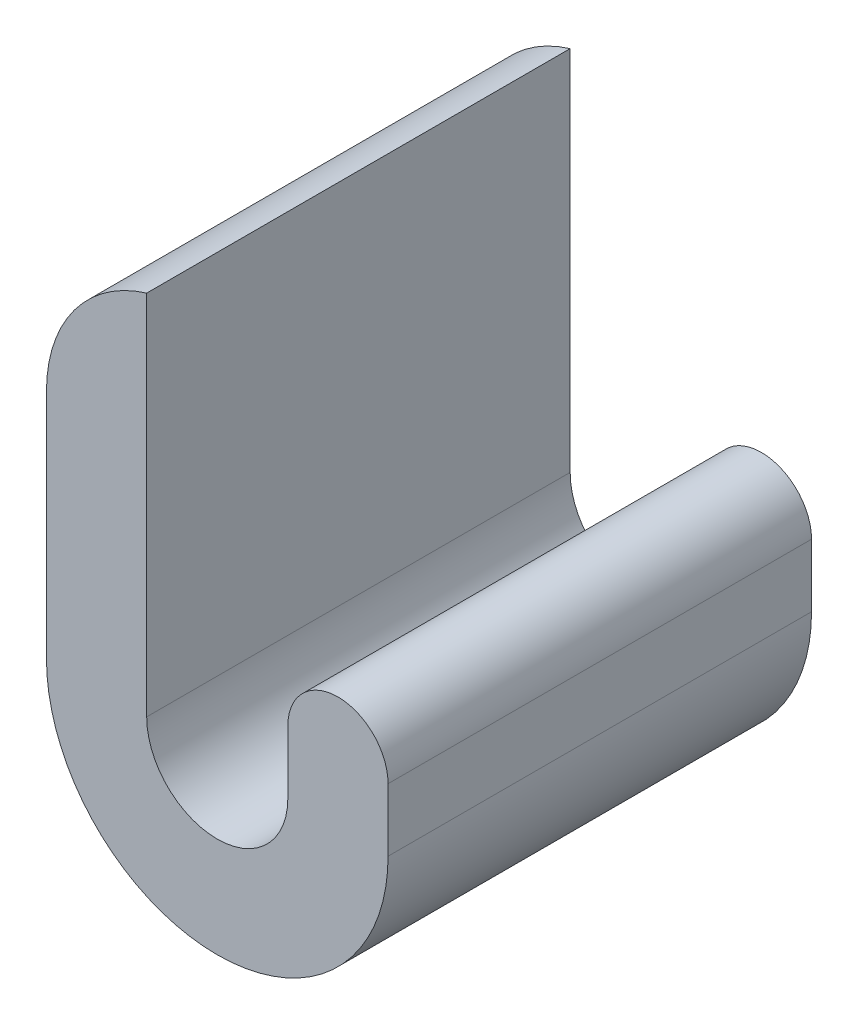
SolidWorks part; units mm, degrees
ref_plane "Front" through (0, 0, 0) normal (0, 0, 1) x (1, 0, 0)
ref_plane "Top" through (0, 0, 0) normal (0, 1, 0) x (1, 0, 0)
ref_plane "Right" through (0, 0, 0) normal (1, 0, 0) x (0, 0, -1)
sketch "Sketch1" plane through (0, 0, 0) normal (0, 0, 1) x (1, 0, 0)
  line L2 (5, 0) -> (5, 8)
  line L3 (5, 8) -> (12.1, 8)
  line L4 (12.1, 8) -> (12.1, 0)
  line L5 (-5, 0) -> (-5, 26)
  line L6 (-5, 26) -> (-12.1, 26)
  line L7 (-12.1, 26) -> (-12.1, 0)
  arc A0 (-5, 0) -> (5, 0) centre (0, 0) ccw
  arc A1 (-12.1, 0) -> (12.1, 0) centre (0, 0) ccw
  circle A3 centre (0, 0) radius 5 construction
  circle A4 centre (0, 0) radius 12.1 construction
  point P1 (21.3333, 0)
  point P8 (12.7507, 3.8983)
  dimension "D1" = 7.1
  dimension "D2" = 26
  dimension "D3" = 8
  dimension "D4" = 5
extrude "Boss-Extrude1" add sketch "Sketch1" against normal blind 30
fillet "Fillet1" radius 10 1 edges at (-12.1, 26, -15)
fillet "Fillet3" 2 edges at (5, 8, -15) (12.1, 8, -15) type full round first side face at (5, 4, -15) second side face at (12.1, 4, -15) middle face at (8.55, 8, -15)
